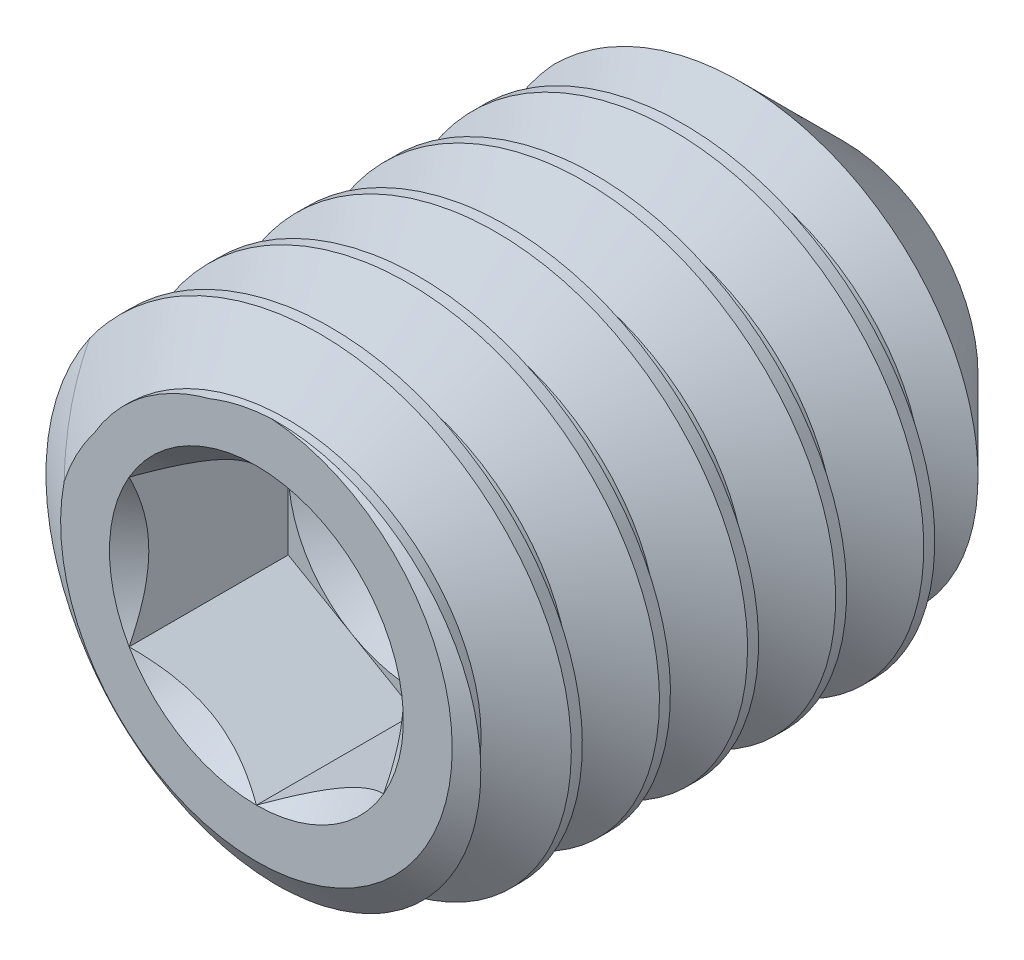
SolidWorks part; units mm, degrees
material "Alloy Steel"
ref_plane "Front" through (0, 0, 0) normal (0, 0, 1) x (1, 0, 0)
ref_plane "Top" through (0, 0, 0) normal (0, 1, 0) x (1, 0, 0)
ref_plane "Right" through (0, 0, 0) normal (1, 0, 0) x (0, 0, -1)
sketch "Sketch22" plane through (0, 0, 0) normal (1, 0, 0) x (0, 0, -1)
  line L0 (-1.2942, 0) -> (-1.2942, 1)
  line L1 (-1.2942, 1) -> (-1.1192, 1.25)
  line L2 (-1.1192, 1.25) -> (1.1407, 1.25)
  line L3 (1.1407, 1.25) -> (1.7058, 0.685)
  line L4 (1.7058, 0.685) -> (1.2942, 0)
  line L5 (1.2942, 0) -> (-1.2942, 0)
  line L6 (1.2942, 0) -> (1.7058, 0) construction
  line L7 (1.7058, 0) -> (1.7058, 0.685) construction
  line L8 (1.7058, -0.685) -> (1.2942, 0) construction
  line L9 (-1.1192, -1.25) -> (1.1407, -1.25) construction
  dimension "Dia" = 2.5
  dimension "Length" = 3
  dimension "D3" = 35
  dimension "D5" = 118
  dimension "D6" = 45
  dimension "D7" = 2
revolve "Revolve1" add sketch "Sketch22" angle 360 about L6
ref_plane "Plane1" through (0, 0, -1.7058) normal (0, 0, 1) x (1, 0, 0)
sketch "Sketch27" plane through (0, 0, -1.7058) normal (0, 0, 1) x (1, 0, 0)
  circle A0 centre (0, 0) radius 1.25 construction
  circle A1 centre (0, 0) radius 1.25
curve "Helix/Spiral1" pitch 0.45 height 3.45 turns 7.6667
sketch "Sketch28" plane through (0, 0, 0) normal (1, 0, 0) x (0, 0, -1)
  line L0 (1.7058, 1.25) -> (2.0995, 1.25)
  line L1 (2.0995, 1.25) -> (1.9308, 0.9577)
  line L2 (1.9308, 0.9577) -> (1.8745, 0.9577)
  line L3 (1.8745, 0.9577) -> (1.7058, 1.25)
  line L4 (1.7902, 1.1039) -> (2.0152, 1.1039) construction
  line L6 (-1.1192, 1.25) -> (1.1407, 1.25) construction
  dimension "D1" = 0.0563
  dimension "D3" = 60
  dimension "D2" = 0.225
sweep "Cut-Sweep2" cut profiles "Sketch28" path "Helix/Spiral1"
sketch "Sketch23" plane through (0, 0, 1.2942) normal (0, 0, 1) x (1, 0, 0)
  line L1 (0, 0.7506) -> (-0.65, 0.3753)
  line L2 (-0.65, 0.3753) -> (-0.65, -0.3753)
  line L3 (-0.65, -0.3753) -> (0, -0.7506)
  line L4 (0, -0.7506) -> (0.65, -0.3753)
  line L5 (0.65, -0.3753) -> (0.65, 0.3753)
  line L6 (0.65, 0.3753) -> (0, 0.7506)
  circle A0 centre (0, 0) radius 0.65 construction
  dimension "Hex" = 1.3
extrude "Cut-Extrude10" cut sketch "Sketch23" against normal blind 0.8125
sketch "Sketch24" plane through (0, 0, 1.2942) normal (0, 0, 1) x (1, 0, 0)
  circle A0 centre (0, 0) radius 0.7506
extrude "Cut-Extrude11" cut sketch "Sketch24" against normal through all draft 45
sketch "Sketch26" plane through (0, 0, 0.4817) normal (0, 0, 1) x (1, 0, 0)
  circle A0 centre (0, 0) radius 0.65 construction
  circle A1 centre (0, 0) radius 0.65
extrude "Cut-Extrude12" cut sketch "Sketch26" against normal through all draft 60
sketch "Sketch30" plane through (0, 0, 0) normal (1, 0, 0) x (0, 0, -1)
  line L0 (-1.1192, 1.25) -> (1.1407, 1.25) construction
  line L1 (-1.2942, 0) -> (-1.2942, 1) construction
  line L2 (1.7058, 0) -> (1.7058, 0.685) construction
  line L3 (-1.1192, -1.25) -> (1.1407, -1.25) construction
  point P0 (-1.2942, 1.25)
  point P1 (1.7058, 1.25)
  point P2 (1.7058, -1.25)
  point P11 (1.0308, -1.25)
  dimension "D1" = 0.675
sketch "Sketch31" plane through (0, 0, 0) normal (1, 0, 0) x (0, 0, -1)
  line L2 (1.2942, 0) -> (1.7058, -0.685)
  line L3 (1.7058, 0.685) -> (1.2942, 0)
equation "\"D7@Sketch22\"=\"Dia@Sketch22\"*.8"
equation "\"D1@Sketch28\" = \"D4@Helix/Spiral1\" * .125"
equation "\"D2@Sketch28\" = \"D4@Helix/Spiral1\" * .5"
equation "\"D3@Helix/Spiral1\" = \"Length@Sketch22\" + \"D4@Helix/Spiral1\""
equation "\"D1@Sketch30\" = \"D4@Helix/Spiral1\" * 1.5"
equation "\"hex Depth@Cut-Extrude10\" = \"Hex@Sketch23\" * .625"
